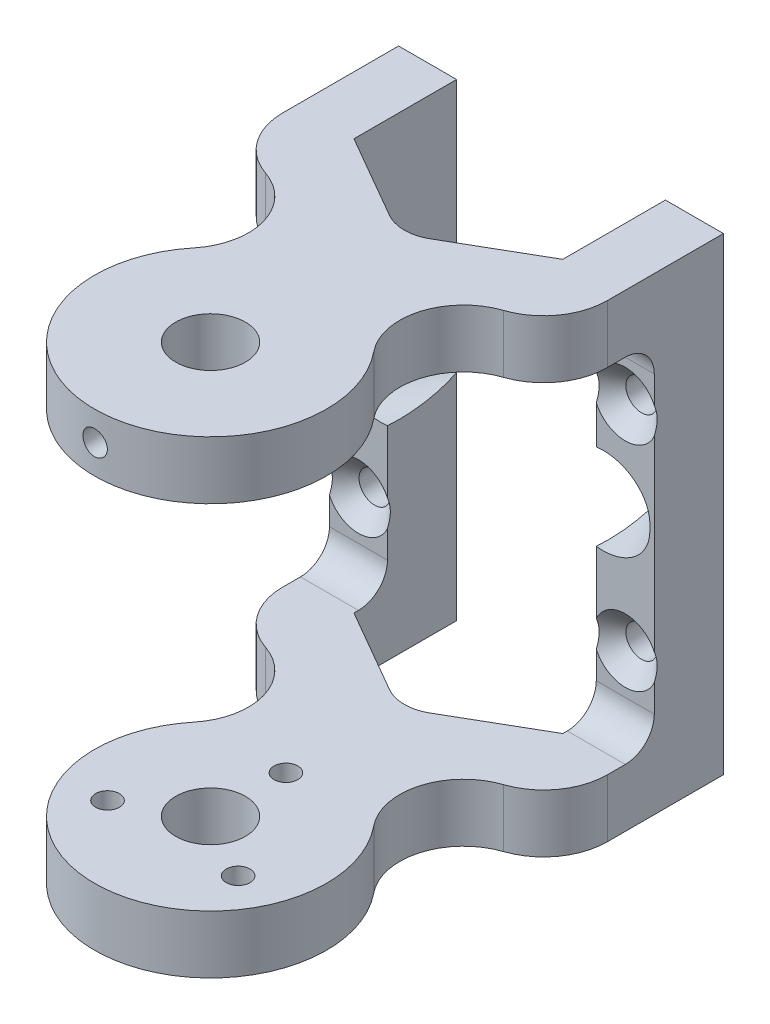
SolidWorks part; units mm, degrees
material "7075-T6 (SN)"
ref_plane "Face" through (0, 0, 0) normal (0, 0, 1) x (1, 0, 0)
ref_plane "Dessus" through (0, 0, 0) normal (0, 1, 0) x (1, 0, 0)
ref_plane "Droite" through (0, 0, 0) normal (1, 0, 0) x (0, 0, -1)
sketch "Esquisse3" plane through (0, 0, 0) normal (0, 1, 0) x (1, 0, 0)
  line L0 (-14, 0) -> (-14, -30.21)
  line L1 (0, 0) -> (0, -30.21) construction
  line L3 (14, -30.21) -> (14, 0)
  line L4 (-14, 0) -> (14, 0)
  line L6 (-14, 0) -> (-14, 3.841) construction
  line L7 (14, 0) -> (14, 6.0564) construction
  circle A0 centre (0, -30.21) radius 3
  arc A1 (-14, -30.21) -> (14, -30.21) centre (0, -30.21) ccw
  dimension "D2" = 6
  dimension "D1" = 28
  dimension "D4" = 30.21
extrude "Boss.-Extru.1" add sketch "Esquisse3" along normal mid plane 40.4
sketch "Esquisse5" plane through (0, 0, 0) normal (1, 0, 0) x (0, 0, -1)
  line L1 (-44.21, 15.2) -> (-19.71, 15.2)
  line L6 (-19.71, 15.2) -> (-19.71, -15.2)
  line L7 (-19.71, -15.2) -> (-44.21, -15.2)
  line L8 (-44.21, 20.2) -> (-44.21, -20.2) construction
  line L9 (-44.21, -15.2) -> (-44.21, 15.2)
  line L10 (-30.21, 20.2) -> (-44.21, 20.2) construction
  line L11 (-44.21, -20.2) -> (-30.21, -20.2) construction
  dimension "D1" = 5
  dimension "D2" = 5
  dimension "D3" = 24.5
extrude "Enlèv. mat.-Extru.2" cut sketch "Esquisse5" against normal through all and the other way through all
sketch "Esquisse6" plane through (0, 0, 0) normal (0, 1, 0) x (1, 0, 0)
  line L0 (-9, 0) -> (-9, -8.848)
  line L4 (-9, -8.848) -> (-1.75, -13.0338)
  line L6 (1.75, -13.0338) -> (9, -8.848)
  line L7 (14, -30.21) -> (14, 0) construction
  line L8 (9, -8.848) -> (9, 0)
  line L9 (9, 0) -> (-9, 0)
  line L11 (0, 0) -> (0, -10.0027) construction
  line L12 (0, -30.21) -> (14, -22.1271) construction
  line L13 (-14, 0) -> (-14, -30.21) construction
  arc A0 (-1.75, -13.0338) -> (1.75, -13.0338) centre (0, -10.0027) ccw
  dimension "D1" = 3.5
  dimension "D2" = 60
  dimension "D3" = 28
  dimension "D4" = 18
  dimension "D5" = 5
extrude "Enlèv. mat.-Extru.3" cut sketch "Esquisse6" against normal through all and the other way through all contours L4 A0 L6 L8 L9 L0 region at (0, 0, 5.7963)
sketch "Esquisse7" plane through (0, -15.2, 0) normal (0, 1, 0) x (1, 0, 0)
  line L0 (0, -30.21) -> (-21, -18.0856) construction
  line L1 (-7, -42.3344) -> (-28, -30.21)
  line L2 (-1.75, -13.0338) -> (-14, -5.9613)
  line L3 (0, -30.21) -> (21, -18.0856) construction
  line L4 (1.75, -13.0338) -> (14, -5.9613)
  line L5 (7, -42.3344) -> (28, -30.21)
  line L6 (0, 0) -> (0, -30.21) construction
  line L7 (-14, 0) -> (-14, -30.21) construction
  line L8 (14, -30.21) -> (14, 0) construction
  line L9 (1.75, -13.0338) -> (9, -8.848) construction
  line L10 (-9, -8.848) -> (-1.75, -13.0338) construction
  arc A0 (-1.75, -13.0338) -> (1.75, -13.0338) centre (0, -10.0027) ccw construction
  arc A1 (-14, -5.9613) -> (-28, -30.21) centre (-21, -18.0856) ccw
  arc A2 (-1.75, -13.0338) -> (1.75, -13.0338) centre (0, -10.0027) ccw
  arc A3 (28, -30.21) -> (14, -5.9613) centre (21, -18.0856) ccw
  arc A4 (-7, -42.3344) -> (7, -42.3344) centre (0, -30.21) ccw
  dimension "D1" = 60
extrude "Enlèv. mat.-Extru.4" cut sketch "Esquisse7" along normal up to surface (30.4 mm away) up to face at (0, 15.2, 33.21)
sketch "Esquisse8" plane through (0, 0, 0) normal (1, 0, 0) x (0, 0, -1)
  line L1 (-8.848, 15.2) -> (-5.9613, 15.2)
  line L2 (-8.848, 15.2) -> (-8.848, -15.2)
  line L3 (-8.848, -15.2) -> (-5.9613, -15.2)
  line L4 (-5.9613, 15.2) -> (-5.9613, -15.2)
extrude "Enlèv. mat.-Extru.5" cut sketch "Esquisse8" against normal through all and the other way through all
fillet "Congé1" radius 2.5 4 edges at (11.5, 15.2, 5.9613) (11.5, -15.2, 5.9613) (-11.5, 15.2, 5.9613) (-11.5, -15.2, 5.9613)
hole_wizard "Fraisage pour vis à tête fraisée M2.51" positions "Esquisse10" profile "Esquisse9" countersink size "M2.5" standard "DIN" end condition up to next
sketch "Esquisse10" plane through (0, 0, 5.9613) normal (0, 0, 1) x (1, 0, 0)
  line L1 (11.5, -9.2) -> (-11.5, -9.2)
  line L2 (11.5, -9.2) -> (11.5, 9.2)
  line L3 (11.5, 9.2) -> (-11.5, 9.2)
  line L4 (-11.5, -9.2) -> (-11.5, 9.2)
  line L5 (11.5, -9.2) -> (-11.5, 9.2) construction
  line L6 (11.5, 9.2) -> (-11.5, -9.2) construction
  line L7 (-11.5, 0) -> (-9, 0) construction
  line L8 (-9, 12.7) -> (-9, -12.7) construction
  line L11 (-11.5, 0) -> (-14, 0) construction
  line L12 (-14, 12.7) -> (-14, -12.7) construction
  line L13 (-14, -20.2) -> (14, -20.2) construction
  point P1 (0, 0)
  point P2 (-11.5, 9.2)
  point P91 (11.5, -9.2)
  point P92 (11.5, 9.2)
  point P93 (-11.5, -9.2)
  dimension "D1" = 11
sketch "Esquisse9" plane through (0, 0, 5.9613) normal (1, 0, 0) x (0, -1, 0)
  line L0 (0, 0) -> (0, 5.9613)
  line L1 (0, 5.9613) -> (1.35, 5.9613)
  line L2 (1.35, 5.9613) -> (1.35, 1.4)
  line L3 (1.35, 1.4) -> (2.75, 0)
  line L5 (2.75, 0) -> (0, 0)
  line L6 (-1.35, 1.4) -> (-2.75, 0) construction
  line L11 (0, -6.35) -> (0, 107.95) construction
  dimension "Diamètre du perçage jusqu'au prochain" = 2.7
  dimension "Profondeur du perçage jusqu'au prochain" = 5.9613
  dimension "Diamètre du fraisage entrant" = 5.5
  dimension "Angle du fraisage entrant" = 90
sketch "Esquisse11" plane through (0, -20.2, 0) normal (0, -1, 0) x (1, 0, 0)
  line L0 (0, 44.21) -> (0, 10.0027) construction
  line L1 (-14, 0) -> (-14, 30.21) construction
  line L3 (14, 10.0027) -> (14, 30.21)
  line L4 (14, 30.21) -> (14, 0) construction
  line L5 (-14, 10.0027) -> (14, 10.0027) construction
  line L6 (-14, 10.0027) -> (-14, 30.21)
  arc A0 (7.7551, 23.8966) -> (-7.7551, 23.8966) centre (0, 30.21) ccw
  arc A1 (-10.2602, 15.2135) -> (-14, 10.0027) centre (-8.5, 10.0027) ccw
  arc A2 (7.7551, 23.8966) -> (10.2602, 15.2135) centre (12.0203, 20.4242) ccw
  arc A3 (14, 30.21) -> (-14, 30.21) centre (0, 30.21) ccw construction
  arc A4 (14, 30.21) -> (-14, 30.21) centre (0, 30.21) ccw
  arc A5 (-7.7551, 23.8966) -> (-10.2602, 15.2135) centre (-12.0203, 20.4242) cw
  arc A6 (10.2602, 15.2135) -> (14, 10.0027) centre (8.5, 10.0027) cw
  arc A7 (1.75, 13.0338) -> (-1.75, 13.0338) centre (0, 10.0027) ccw construction
  dimension "D1" = 20
  dimension "D2" = 5.5
extrude "Enlèv. mat.-Extru.6" cut sketch "Esquisse11" against normal through all
hole_wizard "Trou taraudé M2.51" positions "Esquisse13" profile "Esquisse12" tap size "M2.5" standard "DIN" end condition up to next
sketch "Esquisse13" plane through (0, -20.2, 0) normal (0, 1, 0) x (1, 0, 0)
  line L0 (0, -23.71) -> (-5.6292, -33.46)
  line L1 (-5.6292, -33.46) -> (5.6292, -33.46)
  line L2 (5.6292, -33.46) -> (0, -23.71)
  line L4 (-3, -30.21) -> (-6.5, -30.21) construction
  circle A0 centre (0, -30.21) radius 6.5
  circle A1 centre (0, -30.21) radius 3 construction
  point P6 (0, -23.71)
  point P7 (-5.6292, -33.46)
  point P9 (5.6292, -33.46)
  dimension "D1" = 13
sketch "Esquisse12" plane through (0, -20.2, 23.71) normal (1, 0, 0) x (0, 0, -1)
  line L0 (0, 0) -> (0, 5)
  line L1 (0, 5) -> (1.025, 5)
  line L2 (1.025, 5) -> (1.025, 0)
  line L5 (1.025, 0) -> (0, 0)
  line L11 (0, -6.35) -> (0, 107.95) construction
  dimension "Diamètre du trou pour taraudage jusqu'au prochain" = 2.05
  dimension "Profondeur du trou pour taraudage jusqu'au prochain" = 5
cosmetic thread "Filetage de perçage1" parameters "D2"=2.5
cosmetic thread "Filetage de perçage2" parameters "D2"=2.5
cosmetic thread "Filetage de perçage3" parameters "D2"=2.5
ref_plane "Plan1" through (0, 0, 40.21) normal (0, 0, 1) x (1, 0, 0)
hole_wizard "Diamètre du perçage Ø2.1 (2.1)1" positions "Esquisse15" profile "Esquisse14" hole size "Ø2.1" standard "DIN"
sketch "Esquisse15" plane through (0, 0, 40.21) normal (0, 0, 1) x (1, 0, 0)
  line L0 (0, 20.2) -> (0, 15.2) construction
  line L4 (10, 20.2) -> (-10, 20.2) construction
  line L5 (-10, 15.2) -> (10, 15.2) construction
  point P0 (0, 17.7)
sketch "Esquisse14" plane through (0, 17.7, 40.21) normal (1, 0, 0) x (0, -1, 0)
  line L0 (0, 0) -> (0, 2.4309)
  line L1 (0, 2.4309) -> (1.05, 1.8)
  line L2 (1.05, 1.8) -> (1.05, 0)
  line L5 (1.05, 0) -> (0, 0)
  line L10 (0, 2.4309) -> (-1.05, 1.8) construction
  line L11 (0, -6.35) -> (0, 107.95) construction
  dimension "Diamètre du perçage" = 2.1
  dimension "Profondeur du perçage" = 1.8
  dimension "Angle de pointe" = 118
sketch "Esquisse19" plane through (6.0813, 0, 10.5331) normal (-0.5, 0, -0.866) x (-0.866, 0, 0.5)
  line L0 (-5.3136, 0.8) -> (-5.3136, 1.3) construction
  line L1 (5.0014, -20.2) -> (-3.3702, -20.2) construction
  line L2 (-8.8136, 0.8) -> (-8.8136, 1.3)
  line L3 (-1.8136, 0.8) -> (-1.8136, 1.3)
  line L5 (-4.8136, -8.0544) -> (-4.8136, 8.0544) construction
  arc A0 (-8.8136, 0.8) -> (-1.8136, 0.8) centre (-5.3136, 0.8) ccw
  arc A1 (-1.8136, 1.3) -> (-8.8136, 1.3) centre (-5.3136, 1.3) ccw
  point P4 (-5.3136, 1.05)
  dimension "D1" = 3.5
  dimension "D2" = 21
  dimension "D3" = 0.5
  dimension "D4" = 4
extrude "Enlèv. mat.-Extru.9" cut sketch "Esquisse19" against normal through all and the other way through all
mirror "Symétrie1" about plane through (0, 0, 0) normal (1, 0, 0) of "Enlèv. mat.-Extru.9"
